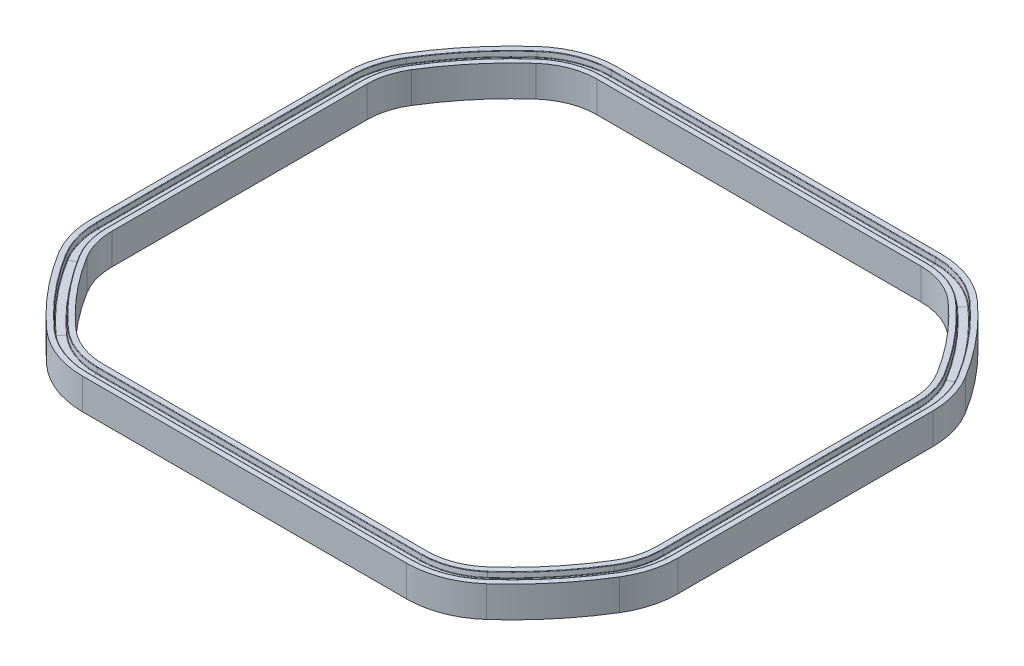
SolidWorks part; units mm, degrees
material "Silicon Rubber"
ref_plane "Front Plane" through (0, 0, 0) normal (0, 0, 1) x (1, 0, 0)
ref_plane "Top Plane" through (0, 0, 0) normal (0, 1, 0) x (1, 0, 0)
ref_plane "Right Plane" through (0, 0, 0) normal (1, 0, 0) x (0, 0, -1)
sketch "ProfileS" plane through (0, 0, 0) normal (0, 1, 0) x (1, 0, 0)
  line L0 (-27.4, 12.339) -> (-27.4, -12.339)
  line L1 (-15.6844, -24.9) -> (15.6844, -24.9)
  line L2 (27.4, -12.339) -> (27.4, 12.339)
  line L3 (15.6844, 24.9) -> (-15.6844, 24.9)
  arc A0 (-27.4, -12.339) -> (-26.2979, -16.2244) centre (-20, -12.339) ccw
  arc A1 (-26.2979, -16.2244) -> (-20.6233, -23.0106) centre (0, 0) ccw
  arc A2 (-20.6233, -23.0106) -> (-15.6844, -24.9) centre (-15.6844, -17.5) ccw
  arc A3 (15.6844, -24.9) -> (20.6233, -23.0106) centre (15.6844, -17.5) ccw
  arc A4 (20.6233, -23.0106) -> (26.2979, -16.2244) centre (0, 0) ccw
  arc A5 (26.2979, -16.2244) -> (27.4, -12.339) centre (20, -12.339) ccw
  arc A6 (27.4, 12.339) -> (26.2979, 16.2244) centre (20, 12.339) ccw
  arc A7 (26.2979, 16.2244) -> (20.6233, 23.0106) centre (0, 0) ccw
  arc A8 (20.6233, 23.0106) -> (15.6844, 24.9) centre (15.6844, 17.5) ccw
  arc A9 (-15.6844, 24.9) -> (-20.6233, 23.0106) centre (-15.6844, 17.5) ccw
  arc A10 (-20.6233, 23.0106) -> (-26.2979, 16.2244) centre (0, 0) ccw
  arc A11 (-26.2979, 16.2244) -> (-27.4, 12.339) centre (-20, 12.339) ccw
  dimension "D1" = 7.4
  dimension "D2" = 7.4
  dimension "D3" = 30.9
  dimension "Length" = 54.8
  dimension "Width" = 49.8
extrude "Profile" add sketch "ProfileS" along normal mid plane 3 thin thin type mid plane wall 2
sketch "GrooveProfileS" plane through (0, 0, 0) normal (0, 0, 1) x (1, 0, 0)
  line L0 (-27.9, 1.5) -> (-26.9, 1.5)
  line L1 (-27.7504, 1) -> (-27.0496, 1)
  line L2 (-27.1489, 1.5) -> (-28.4, 1.5) construction
  line L3 (-28.4, 1.5) -> (-26.4, 1.5) construction
  line L4 (-27.4, 1.5) -> (-27.4, 1) construction
  line L5 (-27.8504, 1.4561) -> (-27.8, 1.0439)
  line L6 (-26.9496, 1.4561) -> (-27, 1.0439)
  arc A0 (-27.9, 1.5) -> (-27.8504, 1.4561) centre (-27.9, 1.45) cw
  arc A1 (-27.7504, 1) -> (-27.8, 1.0439) centre (-27.7504, 1.05) cw
  arc A2 (-27.0496, 1) -> (-27, 1.0439) centre (-27.0496, 1.05) ccw
  arc A3 (-26.9, 1.5) -> (-26.9496, 1.4561) centre (-26.9, 1.45) ccw
  point P12 (-27.4, 1.5)
  dimension "TopRadius" = 0.05
  dimension "BottomRadius" = 0.05
  dimension "TopWidth" = 1
  dimension "Height" = 0.5
  dimension "BottomWidthControl" = 0.1
sweep "GrooveProfile" cut profiles "GrooveProfileS" path "ProfileS<2>"
sketch "ProfileS<2>" plane through (0, 0, 0) normal (0, 1, 0) x (1, 0, 0) same geometry as "ProfileS"
mirror "Mirror1" about plane through (0, 0, 0) normal (0, 1, 0) of "GrooveProfile"
